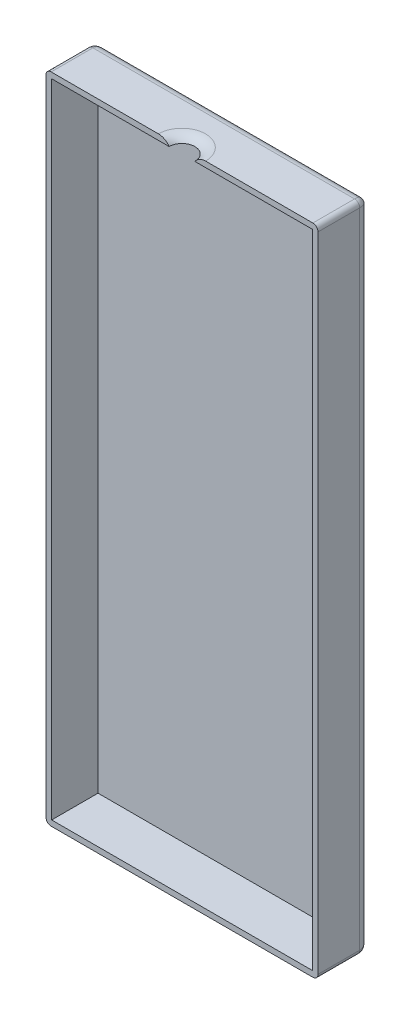
SolidWorks part; units mm, degrees
ref_plane "Plan de face" through (0, 0, 0) normal (0, 0, 1) x (1, 0, 0)
ref_plane "Plan de dessus" through (0, 0, 0) normal (0, 1, 0) x (1, 0, 0)
ref_plane "Plan de droite" through (0, 0, 0) normal (1, 0, 0) x (0, 0, -1)
sketch "Esquisse1" plane through (0, 0, 0) normal (0, 0, 1) x (1, 0, 0)
  line L1 (-28.2911, -78.7359) -> (22.3089, -78.7359)
  line L2 (-28.2911, -78.7359) -> (-28.2911, 45.8641)
  line L3 (-28.2911, 45.8641) -> (22.3089, 45.8641)
  line L4 (22.3089, -78.7359) -> (22.3089, 45.8641)
  dimension "D1" = 50.6
  dimension "D2" = 124.6
extrude "Boss.-Extru.1" add sketch "Esquisse1" along normal blind 9
shell "Coque1" thickness 1.1 removed face at (-2.9911, -16.4359, 9) outward yes
sketch "Esquisse2" plane through (0, 46.9641, 0) normal (0, 1, 0) x (1, 0, 0)
  line L0 (-29.3911, -9) -> (-2.9911, -9) construction
  line L1 (23.4089, -9) -> (-29.3911, -9) construction
  arc A0 (-5.4911, -9) -> (-0.4911, -9) centre (-2.9911, -9) cw
extrude "Enlèv. mat.-Extru.1" cut sketch "Esquisse2" along direction (0, -1, 0) on the side against the normal blind 9 and the other way through all flip side to cut
fillet "Congé1" radius 2.5 1 edges at (-2.9911, 46.9641, 6.5)
fillet "Congé3" radius 2 4 edges at (-2.9911, -79.8359, -1.1) (-2.9911, 46.9641, -1.1) (23.4089, -16.4359, -1.1) (-29.3911, -16.4359, -1.1)
fillet "Congé5" radius 1 8 edges at (-28.8053, -79.2501, -0.5142) (-28.8053, 46.3784, -0.5142) (22.8231, -79.2501, -0.5142) (22.8231, 46.3784, -0.5142) (-29.3911, -79.8359, 4.95) (-29.3911, 46.9641, 4.95) (23.4089, -79.8359, 4.95) (23.4089, 46.9641, 4.95)
